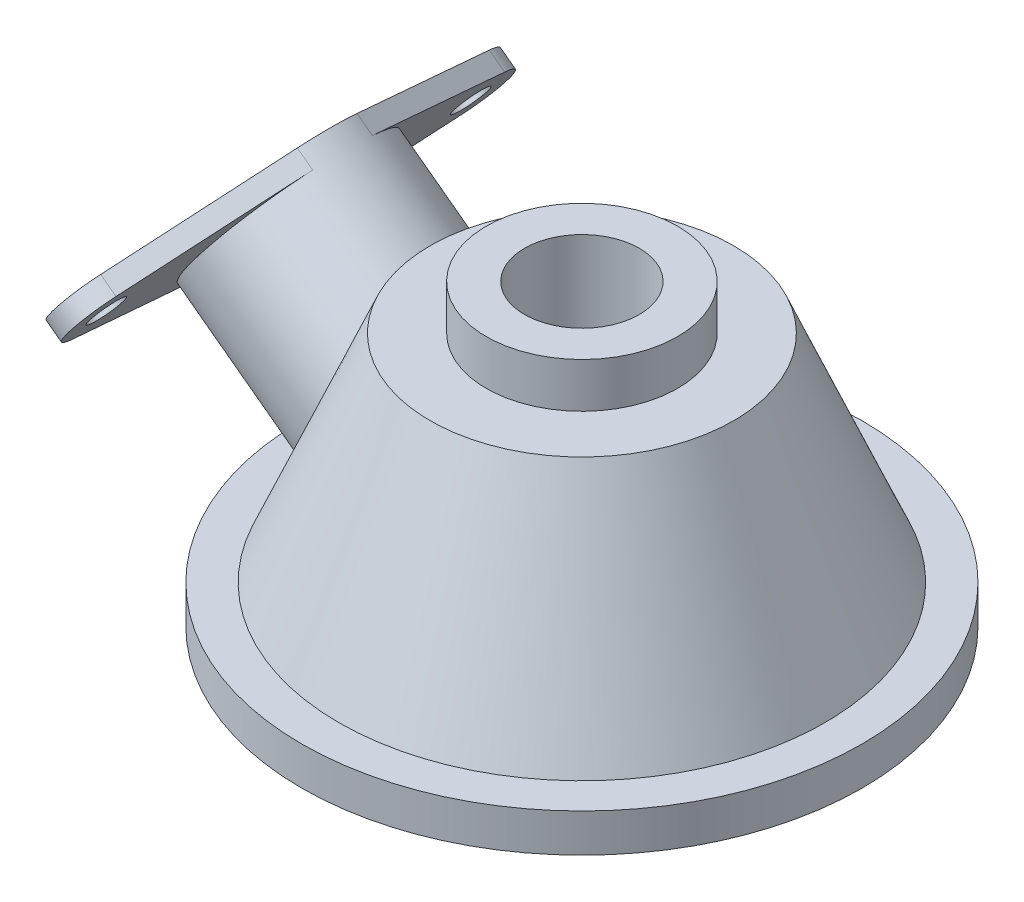
SolidWorks part; units mm, degrees
ref_plane "前视基准面" through (0, 0, 0) normal (0, 0, 1) x (1, 0, 0)
ref_plane "上视基准面" through (0, 0, 0) normal (0, 1, 0) x (1, 0, 0)
ref_plane "右视基准面" through (0, 0, 0) normal (1, 0, 0) x (0, 0, -1)
sketch "草图1" plane through (0, 0, 0) normal (0, 0, 1) x (1, 0, 0)
  line L0 (-15, 78.0911) -> (-25, 78.0911)
  line L1 (-25, 78.0911) -> (-25, 66.3686)
  line L2 (-25, 66.3686) -> (-39.624, 66.3686)
  line L3 (-39.624, 66.3686) -> (-63.5032, 10)
  line L4 (-63.5032, 10) -> (-73.1719, 10)
  line L5 (-73.1719, 10) -> (-73.1719, 0)
  line L6 (-73.1719, 0) -> (-56.8792, 0)
  line L7 (-56.8792, 0) -> (-33, 56.3686)
  line L8 (-33, 56.3686) -> (-15, 56.3686)
  line L9 (-15, 56.3686) -> (-15, 78.0911)
  line L10 (0, 0) -> (0, 29.1224) construction
  point P2 (-44.9396, 28.1843)
  point P11 (-32.312, 66.3686)
  dimension "D1" = 0
  dimension "D2" = 15
  dimension "D3" = 10
  dimension "D4" = 10
  dimension "D5" = 10
  dimension "D6" = 18
  dimension "D7" = 10
revolve "旋转1" add sketch "草图1" angle 360 about L10
sketch "草图3" plane through (0, 0, 0) normal (0, 0, 1) x (1, 0, 0)
  line L0 (0, 0) -> (-80.7054, 59.8194) construction
ref_plane "基准面4" through (-80.7054, 59.8194, 0) normal (-0.8034, 0.5955, 0) x (0, 0, 1)
sketch "草图4" plane through (-80.7054, 59.8194, 0) normal (-0.8034, 0.5955, 0) x (0, 0, 1)
  line L2 (0, -25) -> (0, 25) construction
  line L4 (-7.8014, 23.7516) -> (-50.7582, 9.642)
  line L5 (-50.9259, -9.4752) -> (-12.1603, -21.8432)
  line L6 (50.9259, -9.4752) -> (12.1603, -21.8432)
  line L7 (7.8014, 23.7516) -> (50.7582, 9.642)
  circle A0 centre (0, 0) radius 20
  circle A1 centre (0, 0) radius 25
  circle A2 centre (-47.6093, 0.0551) radius 4.5976
  arc A3 (-50.7582, 9.642) -> (-50.4249, -9.635) centre (-47.6093, 0.0551) ccw
  arc A4 (50.7582, 9.642) -> (50.4249, -9.635) centre (47.6093, 0.0551) cw
  circle A5 centre (47.6093, 0.0551) radius 4.5976
  point P16 (-50.9259, -9.4752)
  point P21 (0, 0)
  dimension "D1" = 40
  dimension "D2" = 50
extrude "凸台-拉伸1" add sketch "草图4" against normal blind 5 separate body contours L4 A3 L5 A1 A2 | A4 L7 A1 L6 A5 region at (-80.5579, 60.0184, -35.6271) region at (-80.5579, 60.0184, 35.6271)
extrude "凸台-拉伸2" add sketch "草图4<3>" against normal up to surface (41.1219 mm away) contours L2 A1 A0 | A1 L2 A0 region at (-94.7923, 40.8139, -6.1412) region at (-94.1035, 41.7433, 0.559) up to face at (0, 10, -63.5032)
sketch "草图4<3>" plane through (-80.7054, 59.8194, 0) normal (-0.8034, 0.5955, 0) x (0, 0, 1) same geometry as "草图4"
extrude "切除-拉伸1" cut sketch "草图4<4>" against normal through all both and the other way through all contours A0
sketch "草图4<4>" plane through (-80.7054, 59.8194, 0) normal (-0.8034, 0.5955, 0) x (0, 0, 1) same geometry as "草图4"
